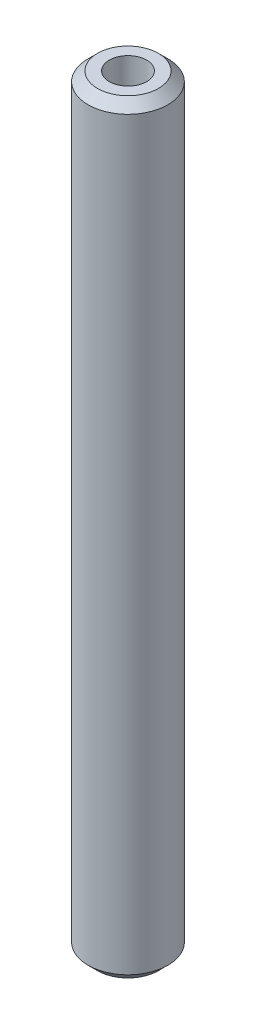
SolidWorks part; units mm, degrees
ref_plane "Front Plane" through (0, 0, 0) normal (0, 0, 1) x (1, 0, 0)
ref_plane "Top Plane" through (0, 0, 0) normal (0, 1, 0) x (1, 0, 0)
ref_plane "Right Plane" through (0, 0, 0) normal (1, 0, 0) x (0, 0, -1)
sketch "Sketch1" plane through (0, 0, 0) normal (0, 1, 0) x (1, 0, 0)
  circle A0 centre (0, 0) radius 20
  dimension "SHAFT_OD" = 40
extrude "Boss-Extrude1" add sketch "Sketch1" along normal blind 383.0817
sketch "Sketch2" plane through (0, 0, 0) normal (0, 1, 0) x (1, 0, 0)
  circle A0 centre (0, 0) radius 9.3727
  dimension "BORE_D" = 18.7454
extrude "Cut-Extrude1" cut sketch "Sketch2" along normal through all
chamfer "Chamfer1" distance 4.7284 angle 45 2 edges at (0, 383.0817, 20) (0, 0, 20)
